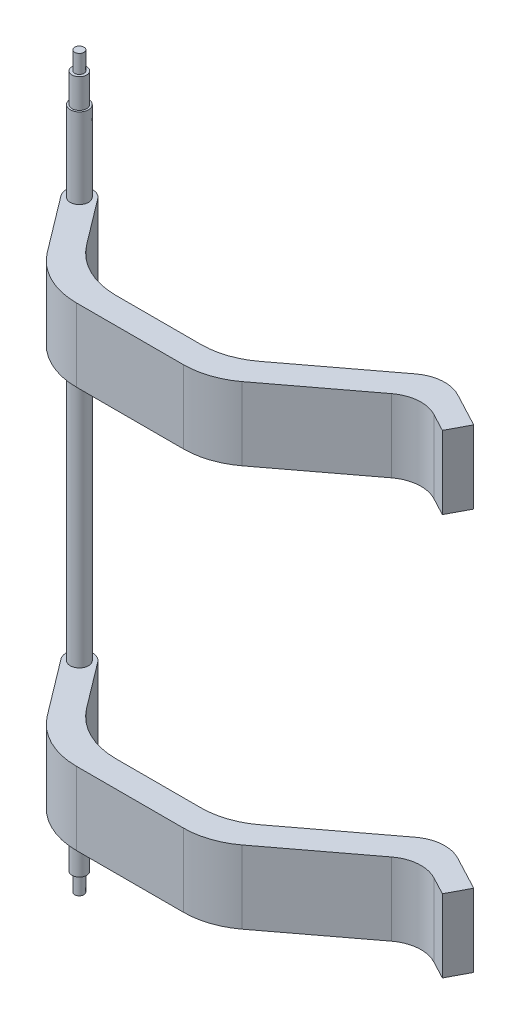
SolidWorks part; units mm, degrees
ref_plane "Front" through (0, 0, 0) normal (0, 0, 1) x (1, 0, 0)
ref_plane "Top" through (0, 0, 0) normal (0, 1, 0) x (1, 0, 0)
ref_plane "Right" through (0, 0, 0) normal (1, 0, 0) x (0, 0, -1)
sketch "Sketch1" plane through (0, 0, 0) normal (0, 0, 1) x (1, 0, 0)
  line L0 (-1.75, 8.7) -> (-1.75, -8.7)
  line L1 (-1.75, 0) -> (-1.5, 0) construction
  line L2 (-1.5, 10) -> (-1.5, -10)
  line L4 (-1.75, -8.7) -> (-1.7, -8.7)
  line L5 (-1.7, -8.7) -> (-1.7, -9.5)
  line L6 (-1.7, -9.5) -> (-1.625, -9.5)
  line L7 (-1.625, -9.5) -> (-1.625, -10)
  line L8 (-1.625, -10) -> (-1.5, -10)
  line L9 (-1.625, 10) -> (-1.5, 10)
  line L10 (-1.625, 9.5) -> (-1.625, 10)
  line L11 (-1.7, 9.5) -> (-1.625, 9.5)
  line L12 (-1.7, 8.7) -> (-1.7, 9.5)
  line L13 (-1.75, 8.7) -> (-1.7, 8.7)
  point P4 (-1.3345, -2.0584)
  dimension "D1" = 0.25
  dimension "D2" = 0.5
  dimension "D3" = 0.05
  dimension "D4" = 0.075
  dimension "D5" = 0.8
  dimension "D6" = 10
  dimension "D7" = 1.5
revolve "Revolve1" add sketch "Sketch1" angle 360 about L2
sketch "Sketch2" plane through (0, 0, 0) normal (0, 1, 0) x (1, 0, 0)
  line L0 (-1.5, 0) -> (9.31, 0) construction
  line L1 (-1.2127, 0.217) -> (0.3341, -1.8307)
  line L2 (0.3341, -1.8307) -> (4.3341, -1.8307)
  line L3 (4.3341, -1.8307) -> (7.8095, 0.7945)
  line L4 (7.8095, 0.7945) -> (9.31, 0)
  line L5 (9.31, 0) -> (9.0127, -0.5615)
  line L6 (9.0127, -0.5615) -> (7.9522, 0)
  line L7 (7.9522, 0) -> (4.5754, -2.5507)
  line L8 (4.5754, -2.5507) -> (-0.0244, -2.5507)
  line L9 (-0.0244, -2.5507) -> (-1.7873, -0.217)
  arc A0 (-1.2127, 0.217) -> (-1.7873, -0.217) centre (-1.5, 0) ccw
  circle A1 centre (-1.5, 0) radius 0.25 construction
  circle A2 centre (-1.5, 0) radius 0.25
  point P1 (0, 0)
  point P4 (1.8465, -2.0125)
  point P15 (9.3224, -0.181)
  point P16 (0, 0)
  point P17 (0, 0)
  point P18 (6.9758, -1.9343)
  point P19 (8.1562, -0.1799)
  point P20 (0, 0)
  point P21 (8.3787, -0.5678)
  point P22 (0, 0)
  point P23 (7.9147, 0)
  point P24 (7.7201, 0.6965)
  point P25 (4.3341, -1.8307)
  point P29 (0, 0)
  point P30 (0, 0)
  dimension "D1" = 0.72
  dimension "D2" = 10.81
  dimension "D3" = 1.2
  dimension "D4" = 0.72
  dimension "D5" = 0.72
  dimension "D6" = 4
extrude "Boss-Extrude1" add sketch "Sketch2" along normal blind 2 from offset 4.5
extrude "Boss-Extrude2" add sketch "Sketch2<2>" along normal blind 2 from offset 6.5 offset against normal yes
sketch "Sketch2<2>" plane through (0, 0, 0) normal (0, 1, 0) x (1, 0, 0) same geometry as "Sketch2"
fillet "Fillet1" radius 2 4 edges at (4.3341, 5.5, 1.8307) (4.3341, -5.5, 1.8307) (0.3341, 5.5, 1.8307) (0.3341, -5.5, 1.8307)
fillet "Fillet2" radius 2 4 edges at (4.5754, -5.5, 2.5507) (-0.0244, -5.5, 2.5507) (4.5754, 5.5, 2.5507) (-0.0244, 5.5, 2.5507)
fillet "Fillet3" radius 1 2 edges at (7.8095, 5.5, -0.7945) (7.8095, -5.5, -0.7945)
fillet "Fillet4" radius 1 2 edges at (7.9522, -5.5, 0) (7.9522, 5.5, 0)
